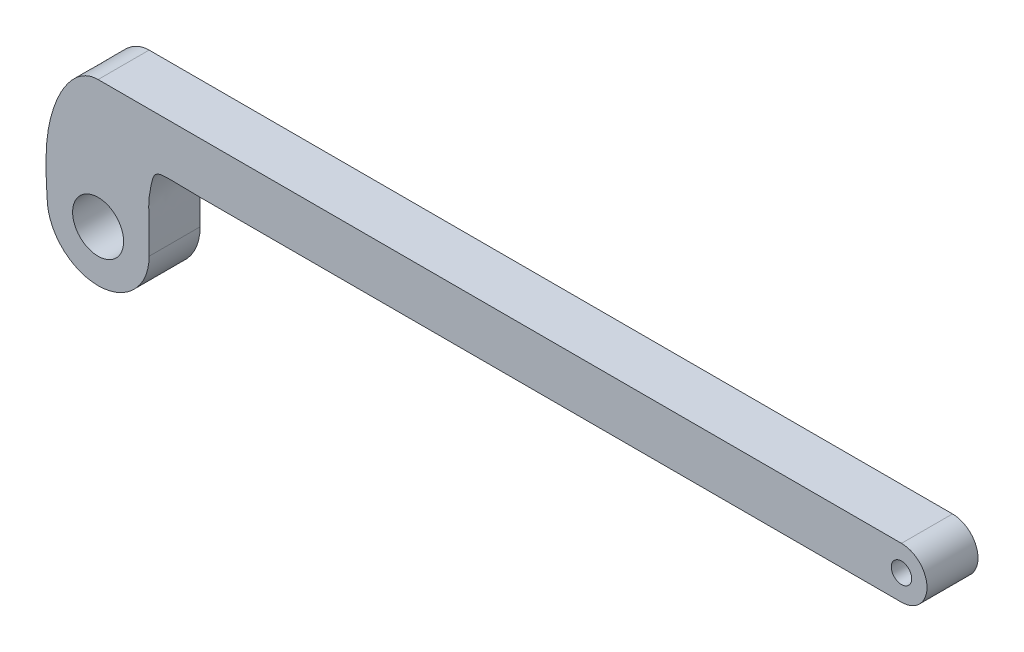
SolidWorks part; units mm, degrees
ref_plane "Front Plane" through (0, 0, 0) normal (1, 0, 0) x (0, 1, 0)
ref_plane "Top Plane" through (0, 0, 0) normal (0, 0, 1) x (0, 1, 0)
ref_plane "Right Plane" through (0, 0, 0) normal (0, 1, 0) x (-1, 0, 0)
sketch "Sketch1" plane through (0, 0, 0) normal (0, 0, 1) x (0, 1, 0)
  line L3 (25, 0) -> (25, -157.485)
  line L4 (15, -20) -> (15, -157.485)
  line L5 (10, 10) -> (10, -10) construction
  circle A0 centre (0, 0) radius 10 construction
  circle A1 centre (20, -157.485) radius 2
  arc A2 (15, -157.485) -> (25, -157.485) centre (20, -157.485) ccw
  circle A5 centre (0, 0) radius 5
  arc A6 (0, 10) -> (0, -10) centre (0, 0) ccw
  spline S0 degree 3 poles (0, 10) (0.6811, 10) (14.2397, 11.4058) (25, 4.9314) (25, 0) knots 0 0 0 0 0.356789 1 1 1 1
  spline S1 degree 3 poles (0, -10) (6.7902, -10) (8.9866, -9.7761) (16.1248, -11.0749) (15, -11.1995) (15, -20) knots 0 0 0 0 0.182752 0.282752 1 1 1 1
  point P23 (10, 0)
  dimension "D1" = 10
  dimension "D6" = 5
  dimension "D2" = 157.485
  dimension "D3" = 10
  dimension "D4" = 20
  dimension "D5" = 10
extrude "Boss-Extrude1" add sketch "Sketch1" along normal blind 10
equation "\"D1@Sketch1\"=\"BearingDiameter\""
equation "\"ThighLength\"= 200"
equation "\"BearingBore\"=4"
equation "\"MinShinWidth\"= 20"
equation "\"HipBore\"=27"
equation "\"ShinThickness\"=10"
equation "\"ThighThickness\"=20"
equation "\"MaxBending\"=135"
equation "\"MaxStretchingAngle\"= 140"
equation "\"ThighJointDistance\"=157.485"
equation "\"PivotDistance\"=40"
equation "\"ShinLength\"=100"
equation "\"BearingDiameter\"= 10"
equation "\"D2@Sketch1\"=\"ThighJointDistance\""
